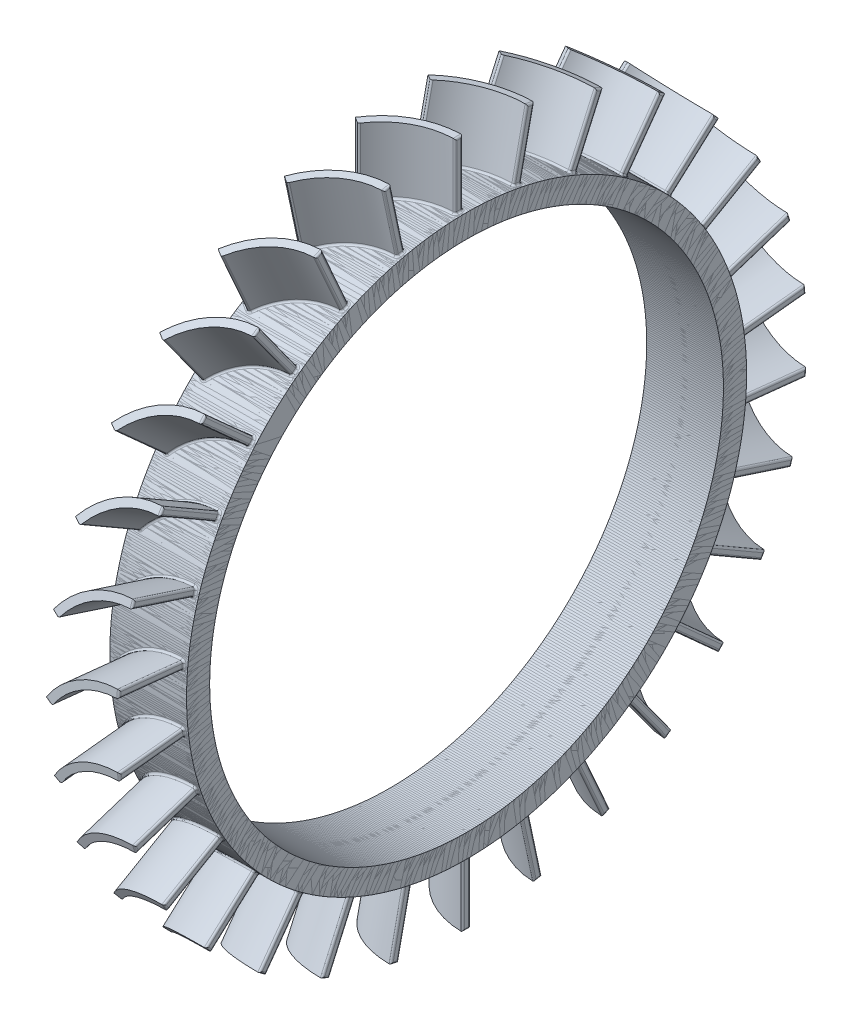
SolidWorks part; units mm, degrees
ref_plane "Front Plane" through (0, 0, 0) normal (0, 0, 1) x (1, 0, 0)
ref_plane "Top Plane" through (0, 0, 0) normal (0, 1, 0) x (1, 0, 0)
ref_plane "Right Plane" through (0, 0, 0) normal (1, 0, 0) x (0, 0, -1)
sketch "Sketch1" plane through (0, 0, 0) normal (1, 0, 0) x (0, 0, -1)
  circle A0 centre (0, 0) radius 73.005
  circle A1 centre (0, 0) radius 67.005
  dimension "D1" = 134.01
  dimension "D2" = 146.01
extrude "Boss-Extrude1" add sketch "Sketch1" along normal mid plane 20
sketch "Sketch2" plane through (0, 0, 0) normal (0, 1, 0) x (1, 0, 0)
  line L0 (-11.0582, 0) -> (12.2549, 0) construction
  line L1 (-10, 73.005) -> (-10, -73.005) construction
  line L2 (10, -73.005) -> (10, 73.005) construction
  line L3 (0, 0) -> (0, 21.2484) construction
  arc A0 (9, 0) -> (-9, 10) centre (9, 21.2) cw
  point P3 (-9, 10)
  point P4 (9, 0)
  dimension "D4" = 21.2
  dimension "D1" = 1
  dimension "D2" = 1
  dimension "D3" = 10
extrude "Extrude-Thin1" add sketch "Sketch2" against normal blind 90 thin
sketch "Sketch3" plane through (10, 0, 0) normal (1, 0, 0) x (0, 0, -1)
  circle A0 centre (0, 0) radius 67.005
  circle A2 centre (0, 0) radius 67.005 construction
extrude "Cut-Extrude1" cut sketch "Sketch3" against normal through all both and the other way through all
fillet "Fillet1" radius 0.5 4 edges at (9, -81.5025, 0) (9, -81.4888, -2) (-7.3019, -81.0814, -11.0566) (9, -90, -1)
fillet "Fillet3" radius 0.5 7 edges at (1.9878, -72.9952, -1.1933) (8.8028, -73.0049, -0.1082) (9, -72.9981, -1.0062) (8.8904, -72.9823, -1.8188) (-8.3603, -72.2607, -10.3981) (-7.3024, -72.1947, -10.8468) (2.6549, -72.9401, -3.0787)
pattern_circular "CirPattern6" count 30 over 360 about axis through (10, 0, 0) along (-1, 0, 0) of bodies 103
